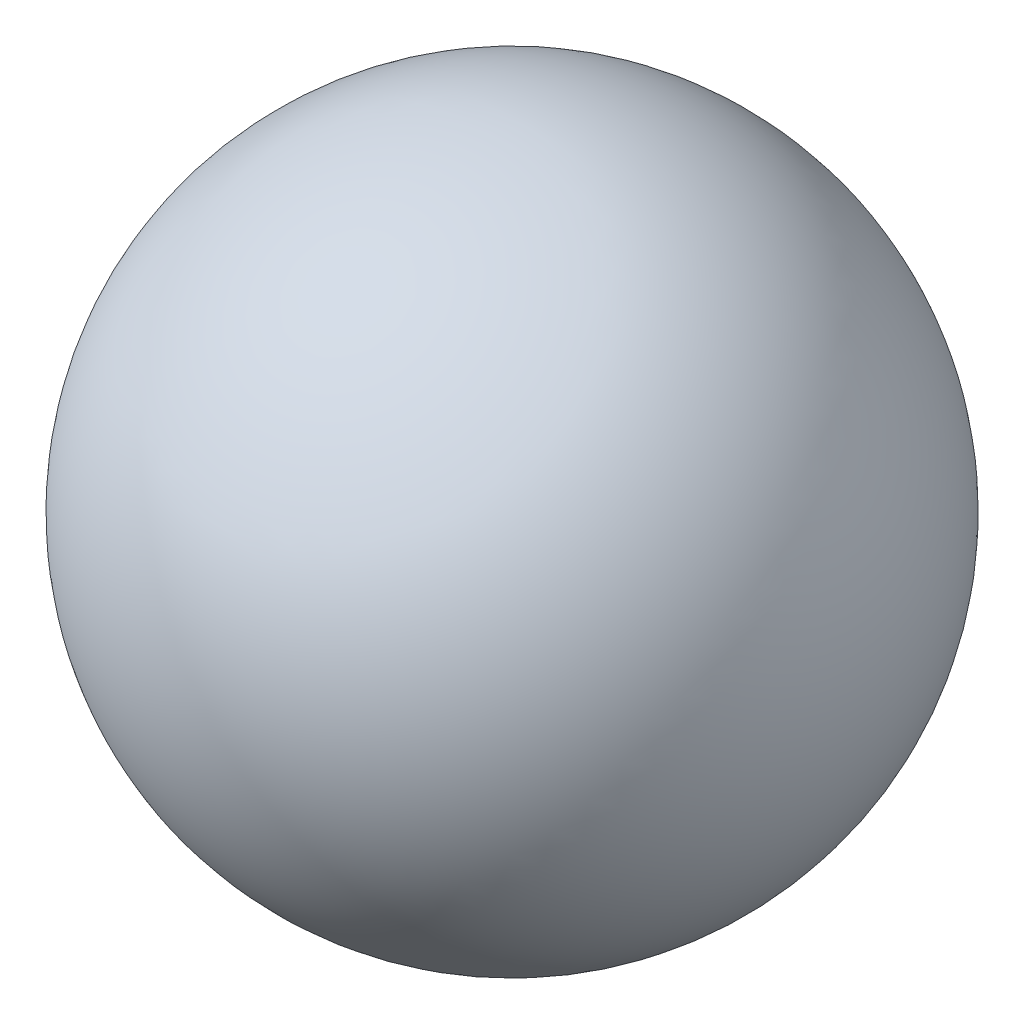
SolidWorks part; units mm, degrees
ref_plane "Front Plane" through (0, 0, 0) normal (0, 0, 1) x (1, 0, 0)
ref_plane "Top Plane" through (0, 0, 0) normal (0, 1, 0) x (1, 0, 0)
ref_plane "Right Plane" through (0, 0, 0) normal (1, 0, 0) x (0, 0, -1)
sketch "Sketch1" plane through (0, 0, 0) normal (1, 0, 0) x (0, 0, -1)
  line L0 (0, 0) -> (-14.2498, 0) construction
  line L1 (0, 0) -> (26.2357, 0) construction
  line L2 (-2.5, 0) -> (2.5, 0)
  arc A0 (2.5, 0) -> (-2.5, 0) centre (0, 0) ccw
  dimension "D1" = 5
revolve "Revolve1" add sketch "Sketch1" angle 360 about L0
ref_axis "Axis1" through (0, 0, 2.75) along (0, 0, -1)
